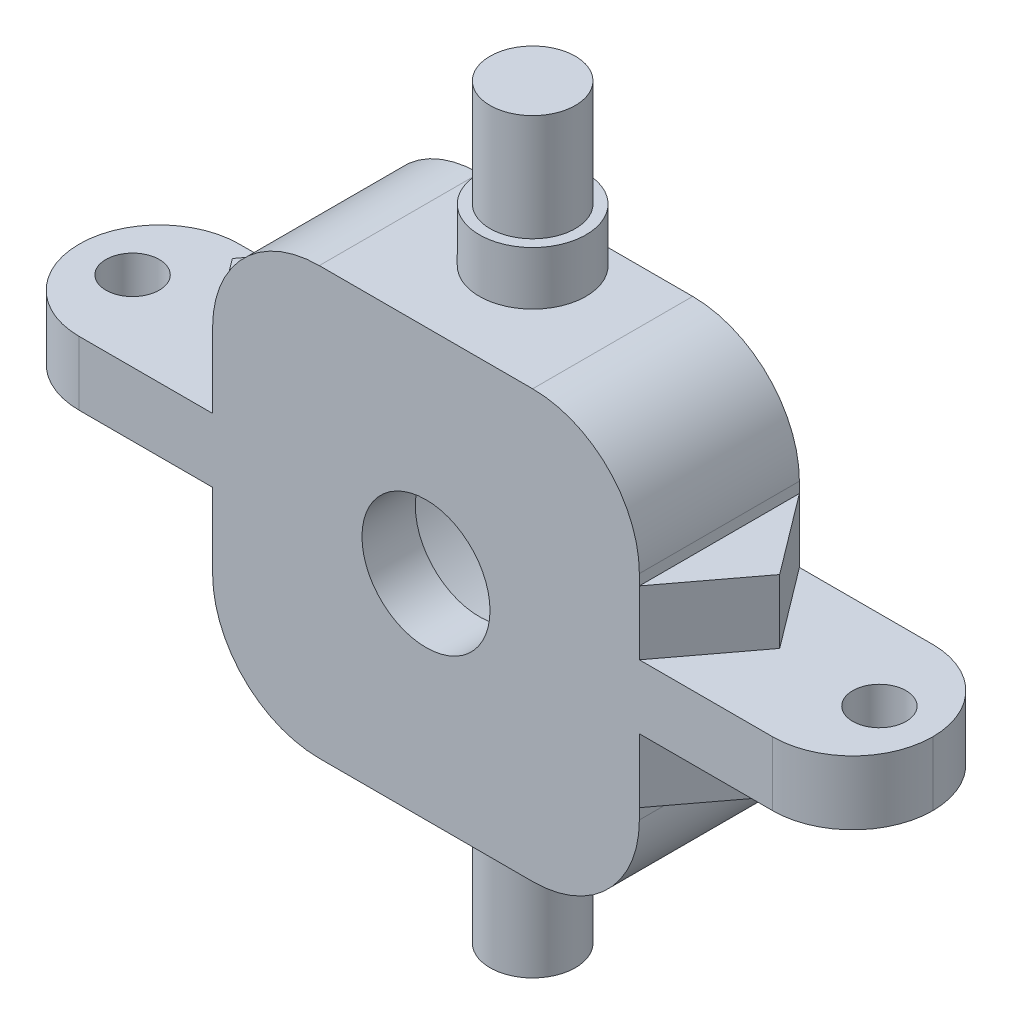
SolidWorks part; units mm, degrees
other "Markup1"
sketch "Sketch14" plane through (-20, -15, 0) normal (-0.9003, -0.4291, -0.0726) x (-0.0804, 0, 0.9968)
ref_plane "Front Plane" through (0, 0, 0) normal (0, 0, 1) x (1, 0, 0)
ref_plane "Top Plane" through (0, 0, 0) normal (0, 1, 0) x (1, 0, 0)
ref_plane "Right Plane" through (0, 0, 0) normal (1, 0, 0) x (0, 0, -1)
sketch "Sketch1" plane through (0, 0, 0) normal (0, 0, 1) x (1, 0, 0)
  line L1 (40, 40) -> (0, 40)
  line L2 (40, 40) -> (40, 0)
  line L3 (40, 0) -> (0, 0)
  line L4 (0, 40) -> (0, 0)
  circle A0 centre (20, 20) radius 6
  dimension "D3" = 12
  dimension "D1" = 40
  dimension "D2" = 40
extrude "Boss-Extrude1" add sketch "Sketch1" along normal blind 15
sketch "Sketch2" plane through (0, 0, 0) normal (0, 0, -1) x (-1, 0, 0)
  circle A0 centre (-20, 20) radius 15
  dimension "D1" = 30
extrude "Cut-Extrude1" cut sketch "Sketch2" against normal blind 10
sketch "Sketch4" plane through (0, 40, 0) normal (0, 1, 0) x (1, 0, 0)
  line L0 (40, 0) -> (0, 0) construction
  circle A0 centre (20, -5) radius 4
  dimension "D1" = 8
  dimension "D2" = 5
extrude "Boss-Extrude2" add sketch "Sketch4" along normal blind 15
sketch "Sketch5" plane through (0, 40, 0) normal (0, 1, 0) x (1, 0, 0)
  circle A0 centre (20, -5) radius 5
extrude "Boss-Extrude3" add sketch "Sketch5" along normal blind 5
sketch "Sketch7" plane through (0, 0, 0) normal (0, -1, 0) x (1, 0, 0)
  line L0 (0, 0) -> (40, 0) construction
  circle A0 centre (20, 5) radius 5
  dimension "D1" = 5
extrude "Boss-Extrude4" add sketch "Sketch7" along normal blind 5
sketch "Sketch8" plane through (0, -5, 0) normal (0, -1, 0) x (1, 0, 0)
  circle A0 centre (20, 5) radius 4
extrude "Boss-Extrude5" add sketch "Sketch8" along normal blind 10
fillet "Fillet1" radius 10 4 edges at (0, 40, 7.5) (0, 0, 7.5) (40, 0, 7.5) (40, 40, 7.5)
sketch "Sketch9" plane through (40, 0, 0) normal (1, 0, 0) x (0, 0, -1)
  line L0 (-15, 20) -> (0, 20) construction
  line L1 (-15, 10) -> (-15, 30) construction
  line L2 (0, 10) -> (0, 30) construction
  line L4 (-15, 17) -> (0, 17)
  line L5 (-15, 17) -> (-15, 23)
  line L6 (-15, 23) -> (0, 23)
  line L7 (0, 17) -> (0, 23)
  line L8 (-15, 17) -> (0, 23) construction
  line L9 (-15, 23) -> (0, 17) construction
  point P6 (-7.5, 20)
  dimension "D1" = 6
extrude "Boss-Extrude6" add sketch "Sketch9" along normal blind 20
sketch "Sketch10" plane through (0, 0, 0) normal (-1, 0, 0) x (0, 0, 1)
  line L1 (0, 17) -> (15, 17)
  line L2 (0, 17) -> (0, 23)
  line L3 (0, 23) -> (15, 23)
  line L4 (15, 17) -> (15, 23)
extrude "Boss-Extrude7" add sketch "Sketch10" along normal blind 20
sketch "Sketch11" plane through (0, 23, 0) normal (0, 1, 0) x (1, 0, 0)
  line L0 (50, 0) -> (50, -15) construction
  line L1 (60, 0) -> (40, 0) construction
  line L2 (60, -15) -> (40, -15) construction
  line L3 (60, 0) -> (60, -15) construction
  line L5 (-20, -15) -> (0, -15) construction
  line L10 (-20, -15) -> (-20, 0) construction
  circle A0 centre (-15, -7.5) radius 2.5
  circle A1 centre (55, -7.5) radius 2.5
  dimension "D1" = 5
  dimension "D2" = 5
  dimension "D6" = 5
  dimension "D3" = 7.5
  dimension "D4" = 7.5
  dimension "D5" = 5
extrude "Cut-Extrude2" cut sketch "Sketch11" against normal up to next
fillet "Fillet2" radius 7.5 4 edges at (-20, 20, 15) (-20, 20, 0) (60, 20, 15) (60, 20, 0)
sketch "Sketch12" plane through (0, 23, 0) normal (0, 1, 0) x (1, 0, 0)
  line L2 (0, 0) -> (0, -15)
  line L3 (0, -7.5) -> (-20, -7.5) construction
  line L4 (0, 0) -> (-5.6517, -7.5)
  line L5 (-5.6517, -7.5) -> (0, -15)
  line L6 (20, -15) -> (20, 0) construction
  line L7 (30, -15) -> (10, -15) construction
  line L8 (45.6517, -7.5) -> (40, -15)
  line L9 (40, 0) -> (45.6517, -7.5)
  line L10 (40, 0) -> (40, -15)
  circle A0 centre (20, -5) radius 5 construction
  dimension "D1" = 37
extrude "Boss-Extrude8" add sketch "Sketch12" along normal blind 6
sketch "Sketch13" plane through (0, 17, 0) normal (0, -1, 0) x (1, 0, 0)
  line L0 (0, 15) -> (-5.6517, 7.5)
  line L1 (-5.6517, 7.5) -> (0, 0)
  line L2 (0, 0) -> (0, 15)
  line L3 (40, 15) -> (45.6517, 7.5)
  line L4 (45.6517, 7.5) -> (40, 0)
  line L5 (40, 0) -> (40, 15)
extrude "Boss-Extrude9" add sketch "Sketch13" along normal blind 6
